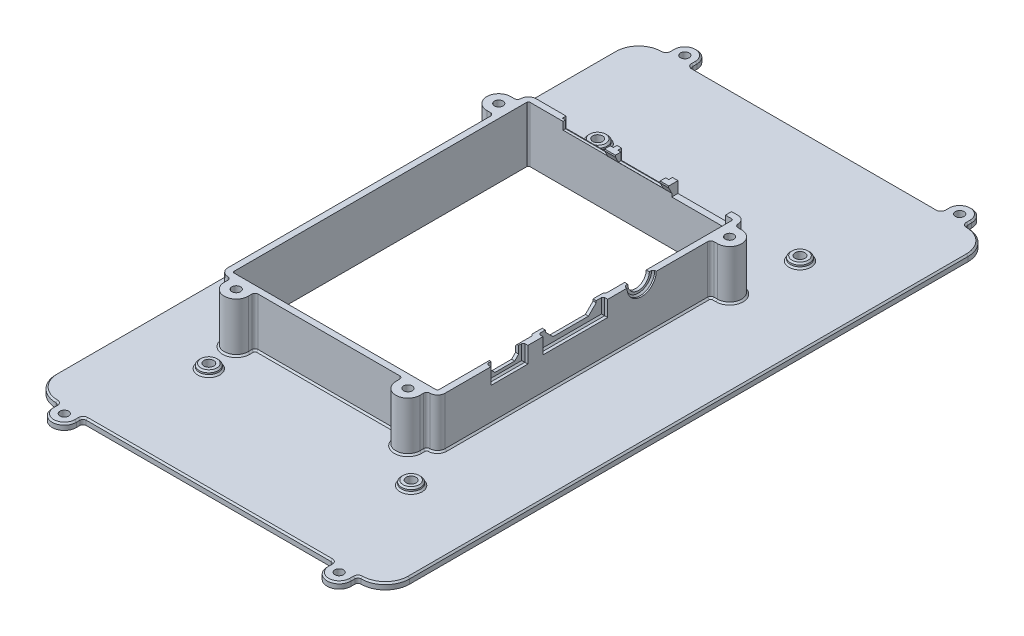
SolidWorks part; units mm, degrees
ref_plane "Front Plane" through (0, 0, 0) normal (0, 0, 1) x (1, 0, 0)
ref_plane "Top Plane" through (0, 0, 0) normal (0, 1, 0) x (1, 0, 0)
ref_plane "Right Plane" through (0, 0, 0) normal (1, 0, 0) x (0, 0, -1)
sketch "Sketch2" plane through (0, 0, 0) normal (0, 1, 0) x (1, 0, 0)
  line L1 (2.5, 0) -> (68, 0)
  line L2 (0, 2.5) -> (0, 97.5)
  line L3 (2.5, 100) -> (68, 100)
  line L4 (70.5, 2.5) -> (70.5, 97.5)
  arc A0 (0, 2.5) -> (2.5, 0) centre (2.5, 2.5) ccw
  arc A1 (68, 0) -> (70.5, 2.5) centre (68, 2.5) ccw
  arc A2 (70.5, 97.5) -> (68, 100) centre (68, 97.5) ccw
  arc A3 (2.5, 100) -> (0, 97.5) centre (2.5, 97.5) ccw
  point P7 (0, 0)
  point P10 (70.5, 0)
  point P13 (70.5, 100)
  point P16 (0, 100)
  dimension "D3" = 2.5
  dimension "D1" = 70.5
  dimension "D2" = 100
extrude "Base" add sketch "Sketch2" along normal blind 16.1
shell "Shell" thickness 2 removed face at (35.25, 16.1, -50) removed face at (35.25, 0, -50)
sketch "Sketch14" plane through (0, 0, 0) normal (0, -1, 0) x (1, 0, 0)
  line L0 (35.25, 0) -> (35.25, -100) construction
  line L2 (68, -100) -> (2.5, -100) construction
  line L3 (-2.2, -88.7) -> (0, -88.7)
  line L4 (0, -97.5) -> (0, -2.5) construction
  line L5 (0, -88.7) -> (0, -96.5)
  line L6 (0, -96.5) -> (-2.2, -96.5)
  line L7 (3.5, 2.2) -> (3.5, 0)
  line L8 (2.5, 0) -> (68, 0) construction
  line L9 (3.5, 0) -> (11.3, 0)
  line L10 (11.3, 0) -> (11.3, 2.2)
  line L11 (72.7, -88.7) -> (70.5, -88.7)
  line L12 (70.5, -96.5) -> (72.7, -96.5)
  line L13 (70.5, -88.7) -> (70.5, -96.5)
  line L14 (59.2, 0) -> (59.2, 2.2)
  line L15 (67, 0) -> (59.2, 0)
  line L16 (67, 2.2) -> (67, 0)
  line L17 (2.5, 0) -> (68, 0) construction
  arc A0 (-2.2, -88.7) -> (-2.2, -96.5) centre (-2.2, -92.6) ccw
  arc A1 (3.5, 2.2) -> (11.3, 2.2) centre (7.4, 2.2) cw
  arc A2 (72.7, -88.7) -> (72.7, -96.5) centre (72.7, -92.6) cw
  arc A3 (67, 2.2) -> (59.2, 2.2) centre (63.1, 2.2) ccw
  dimension "D1" = 2.2
  dimension "D2" = 7.8
  dimension "D3" = 3.5
  dimension "D4" = 3.5
extrude "Board Clamps" add sketch "Sketch14" against normal up to surface (16.1 mm away) up to face at (35.25, 16.1, -50)
fillet "Board Clamp Fillets" radius 1 8 edges at (59.2, 8.05, 0) (67, 8.05, 0) (11.3, 8.05, 0) (3.5, 8.05, 0) (0, 8.05, -96.5) (0, 8.05, -88.7) (70.5, 8.05, -88.7) (70.5, 8.05, -96.5)
sketch "Sketch7" plane through (0, 0, -100) normal (0, 0, -1) x (-1, 0, 0)
  line L0 (-68, 16.1) -> (-2.5, 16.1) construction
  line L1 (-65.95, 16.1) -> (-48.55, 16.1)
  line L2 (-65.95, 16.1) -> (-65.95, 12.5)
  line L3 (-65.95, 12.5) -> (-48.55, 12.5)
  line L4 (-48.55, 16.1) -> (-48.55, 12.5)
  line L5 (-70.5, 16.1) -> (-70.5, 0) construction
  line L6 (-45.75, 16.1) -> (-31.25, 16.1)
  line L7 (-45.75, 16.1) -> (-45.75, 13.63)
  line L8 (-45.75, 13.63) -> (-31.25, 13.63)
  line L9 (-31.25, 16.1) -> (-31.25, 13.63)
  line L10 (-27.75, 16.1) -> (-13.25, 16.1)
  line L11 (-27.75, 16.1) -> (-27.75, 13.63)
  line L12 (-27.75, 13.63) -> (-13.25, 13.63)
  line L13 (-13.25, 16.1) -> (-13.25, 13.63)
  dimension "D1" = 14.5
  dimension "D2" = 2.47
  dimension "D3" = 17.4
  dimension "D4" = 3.6
  dimension "D5" = 4.55
  dimension "D6" = 24.75
  dimension "D7" = 42.75
extrude "IO Cutout" cut sketch "Sketch7" against normal blind 2
sketch "Sketch8" plane through (0, 0, -100) normal (0, 0, -1) x (-1, 0, 0)
  line L6 (-30.25, 12.63) -> (-30.25, 16.1)
  line L7 (-46.75, 12.63) -> (-30.25, 12.63)
  line L8 (-46.75, 16.1) -> (-46.75, 12.63)
  line L9 (-30.25, 12.63) -> (-30.25, 16.1)
  line L10 (-46.75, 12.63) -> (-30.25, 12.63)
  line L11 (-46.75, 16.1) -> (-46.75, 12.63)
  line L12 (-46.75, 16.1) -> (-30.25, 16.1)
  line L13 (-28.75, 16.1) -> (-12.25, 16.1)
  line L15 (-12.25, 12.63) -> (-12.25, 16.1)
  line L16 (-28.75, 12.63) -> (-12.25, 12.63)
  line L17 (-28.75, 16.1) -> (-28.75, 12.63)
  line L18 (-12.25, 12.63) -> (-12.25, 16.1)
  line L19 (-28.75, 12.63) -> (-12.25, 12.63)
  line L20 (-28.75, 16.1) -> (-28.75, 12.63)
  dimension "D1" = 1
  dimension "D2" = 1
extrude "IO Approach" cut sketch "Sketch8" against normal blind 1.2
sketch "Sketch9" plane through (48.55, 0, 0) normal (1, 0, 0) x (0, 0, -1)
  line L0 (98, 16.1) -> (97, 16.1)
  line L1 (97, 16.1) -> (97, 15.55)
  line L2 (97, 15.55) -> (98, 13.55)
  line L3 (98, 13.55) -> (98, 16.1)
  dimension "D1" = 1
  dimension "D2" = 0.55
  dimension "D3" = 2.55
extrude "IO Support" add sketch "Sketch9" against normal up to surface (20.8 mm away) up to face at (27.75, 14.865, -98.4)
sketch "Sketch10" plane through (0, 0, -98) normal (0, 0, -1) x (-1, 0, 0)
  line L1 (-45.75, 16.1) -> (-31.25, 16.1)
  line L2 (-45.75, 16.1) -> (-45.75, 13.63)
  line L3 (-45.75, 13.63) -> (-31.25, 13.63)
  line L4 (-31.25, 16.1) -> (-31.25, 13.63)
extrude "IO Support Cutout" cut sketch "Sketch10" against normal blind 1
sketch "Sketch11" plane through (68.5, 0, 0) normal (-1, 0, 0) x (0, 0, 1)
  line L0 (-2.5, 16.1) -> (-97.5, 16.1) construction
  line L1 (-56.75, 16.1) -> (-32.75, 16.1)
  line L2 (-56.75, 16.1) -> (-56.75, 11.48)
  line L3 (-56.75, 11.48) -> (-32.75, 11.48)
  line L4 (-32.75, 16.1) -> (-32.75, 11.48)
  line L5 (0, 16.1) -> (0, 0) construction
  line L6 (-30.85, 16.1) -> (-15.85, 16.1)
  line L7 (-30.85, 16.1) -> (-30.85, 10.35)
  line L8 (-30.85, 10.35) -> (-15.85, 10.35)
  line L9 (-15.85, 16.1) -> (-15.85, 10.35)
  dimension "D1" = 15.85
  dimension "D2" = 15
  dimension "D3" = 5.75
  dimension "D4" = 4.62
  dimension "D5" = 24
  dimension "D6" = 32.75
extrude "HDMI Support" add sketch "Sketch11" along normal blind 0.5
chamfer "HDMI Support Chamfer" distance 0.5 angle 45 7 edges at (68, 16.1, -23.35) (68, 13.225, -15.85) (68, 10.35, -23.35) (68, 13.225, -30.85) (68, 13.79, -56.75) (68, 11.48, -44.75) (68, 13.79, -32.75)
sketch "Sketch12" plane through (70.5, 0, 0) normal (1, 0, 0) x (0, 0, -1)
  line L0 (2.5, 16.1) -> (87.7, 16.1) construction
  line L1 (17.35, 16.1) -> (29.35, 16.1)
  line L2 (17.35, 16.1) -> (17.35, 10.85)
  line L3 (17.35, 10.85) -> (29.35, 10.85)
  line L4 (29.35, 16.1) -> (29.35, 10.85)
  line L5 (0, 16.1) -> (0, 0) construction
  line L7 (34.25, 16.1) -> (55.25, 16.1)
  line L8 (34.25, 16.1) -> (34.25, 10.98)
  line L9 (34.25, 10.98) -> (55.25, 10.98)
  line L10 (55.25, 16.1) -> (55.25, 10.98)
  dimension "D1" = 17.35
  dimension "D2" = 12
  dimension "D3" = 5.25
  dimension "D4" = 34.25
  dimension "D5" = 21
  dimension "D6" = 5.12
extrude "HDMI Approach" cut sketch "Sketch12" against normal blind 1.5
sketch "Sketch13" plane through (69, 0, 0) normal (1, 0, 0) x (0, 0, -1)
  line L3 (18.85, 16.1) -> (27.85, 16.1)
  line L4 (36.5, 16.1) -> (36.5, 12.98)
  line L5 (55.25, 16.1) -> (34.25, 16.1) construction
  line L6 (27.85, 12.35) -> (27.85, 16.1)
  line L7 (18.85, 12.35) -> (27.85, 12.35)
  line L8 (18.85, 16.1) -> (18.85, 12.35)
  line L9 (27.85, 12.35) -> (27.85, 16.1)
  line L10 (18.85, 12.35) -> (27.85, 12.35)
  line L11 (18.85, 16.1) -> (18.85, 12.35)
  line L12 (36.5, 12.98) -> (53, 12.98)
  line L13 (53, 12.98) -> (53, 16.1)
  line L14 (53, 16.1) -> (36.5, 16.1)
  line L15 (34.25, 16.1) -> (34.25, 10.98) construction
  line L16 (55.25, 10.98) -> (55.25, 16.1) construction
  line L17 (34.25, 10.98) -> (55.25, 10.98) construction
  dimension "D2" = 2.25
  dimension "D3" = 2.25
  dimension "D4" = 2
  dimension "D1" = 1.5
extrude "HDMI Cutout" cut sketch "Sketch13" against normal blind 1
chamfer "HDMI Approach Chamfer" distance 0.5 angle 45 6 edges at (69, 13.475, -17.35) (69, 10.85, -23.35) (69, 13.475, -29.35) (69, 13.54, -34.25) (69, 10.98, -44.75) (69, 13.54, -55.25)
chamfer "USB Chamfer" distance 1.3 angle 45 2 edges at (68.5, 12.35, -18.85) (68.5, 12.35, -27.85)
chamfer "HDMI Chamfer" distance 2.5 angle 45 2 edges at (68.5, 12.98, -36.5) (68.5, 12.98, -53)
sketch "Sketch16" plane through (70.5, 0, 0) normal (1, 0, 0) x (0, 0, -1)
  line L1 (2.5, 16.1) -> (17.35, 16.1) construction
  line L2 (0, 16.1) -> (0, 0) construction
  circle A0 centre (66.25, 16.1) radius 3.5
  dimension "D2" = 7
  dimension "D1" = 66.25
extrude "Audio Cutout" cut sketch "Sketch16" against normal blind 2
sketch "Sketch17" plane through (70.5, 0, 0) normal (1, 0, 0) x (0, 0, -1)
  circle A0 centre (66.25, 16.1) radius 4.75
  dimension "D1" = 9.5
extrude "Audio Approach" cut sketch "Sketch17" against normal blind 1
chamfer "Audio Approach Chamfer" distance 0.5 angle 45 1 edges at (69.5, 11.35, -66.25)
sketch "Board Location" plane through (0, 0, 0) normal (0, 1, 0) x (1, 0, 0)
  line L0 (39.5, 100) -> (39.5, 0) construction
  line L1 (68, 100) -> (65.95, 100) construction
  line L3 (0, 87.7) -> (0, 2.5) construction
  line L4 (12.3, 0) -> (58.2, 0) construction
  line L5 (0, 87.7) -> (0, 2.5) construction
  circle A0 centre (15, 74.25) radius 1.4
  circle A1 centre (15, 16.25) radius 1.4
  circle A2 centre (64, 16.25) radius 1.4
  circle A3 centre (64, 74.25) radius 1.4
  dimension "D1" = 2.8
  dimension "D2" = 25.75
  dimension "D3" = 83.75
  dimension "D4" = 15
  dimension "D5" = 39.5
sketch "Sketch19" plane through (0, 0, 0) normal (0, -1, 0) x (1, 0, 0)
  line L1 (-6.55, 46.74) -> (92.45, 46.74)
  line L2 (-14.43, 38.86) -> (-14.43, -142.34)
  line L3 (-6.55, -150.22) -> (92.45, -150.22)
  line L4 (100.33, 38.86) -> (100.33, -142.34)
  line L12 (2.5, -98) -> (68, -98)
  line L13 (68.5, -97.5) -> (68.5, -2.5)
  line L14 (68, -2) -> (2.5, -2)
  line L15 (2, -2.5) -> (2, -97.5)
  line L16 (2.5, -98) -> (68, -98)
  line L17 (68.5, -97.5) -> (68.5, -2.5)
  line L18 (68, -2) -> (2.5, -2)
  line L19 (2, -2.5) -> (2, -97.5)
  arc A0 (-14.43, -142.34) -> (-6.55, -150.22) centre (-6.55, -142.34) ccw
  arc A1 (92.45, -150.22) -> (100.33, -142.34) centre (92.45, -142.34) ccw
  arc A2 (100.33, 38.86) -> (92.45, 46.74) centre (92.45, 38.86) ccw
  arc A3 (-6.55, 46.74) -> (-14.43, 38.86) centre (-6.55, 38.86) ccw
  arc A12 (2, -97.5) -> (2.5, -98) centre (2.5, -97.5) ccw
  arc A13 (68, -98) -> (68.5, -97.5) centre (68, -97.5) ccw
  arc A14 (68.5, -2.5) -> (68, -2) centre (68, -2.5) ccw
  arc A15 (2.5, -2) -> (2, -2.5) centre (2.5, -2.5) ccw
  arc A16 (2, -97.5) -> (2.5, -98) centre (2.5, -97.5) ccw
  arc A17 (68, -98) -> (68.5, -97.5) centre (68, -97.5) ccw
  arc A18 (68.5, -2.5) -> (68, -2) centre (68, -2.5) ccw
  arc A19 (2.5, -2) -> (2, -2.5) centre (2.5, -2.5) ccw
  point P7 (-14.43, -150.22)
  point P12 (100.33, 46.74)
  point P15 (-14.43, 46.74)
  dimension "D5" = 7.88
  dimension "D1" = 62.99
  dimension "D2" = 29.43
  dimension "D3" = 114.76
  dimension "D4" = 196.96
  dimension "D6" = 0
extrude "Screen Base" add sketch "Sketch19" along normal blind 2
sketch "Sketch15" plane through (0, 16.1, 0) normal (0, 1, 0) x (1, 0, 0)
  circle A0 centre (-2.2, 92.6) radius 1.4
  circle A1 centre (72.7, 92.6) radius 1.4
  circle A2 centre (63.1, -2.2) radius 1.4
  circle A3 centre (7.4, -2.2) radius 1.4
  arc A4 (72.7, 88.7) -> (72.7, 96.5) centre (72.7, 92.6) ccw construction
  dimension "D1" = 2.8
extrude "Board Clamp Taps" cut sketch "Sketch15" against normal through all
sketch "Sketch20" plane through (0, 0, 0) normal (0, 1, 0) x (1, 0, 0)
  circle A0 centre (9.15, 113.35) radius 3.1
  circle A1 centre (74.8, 113.35) radius 3.1
  circle A2 centre (74.8, -12.85) radius 3.1
  circle A3 centre (9.15, -12.85) radius 3.1
  dimension "D5" = 6.2
  dimension "D1" = 29.1
  dimension "D2" = 126.2
  dimension "D3" = 5.85
  dimension "D4" = 65.65
extrude "Leg Supports" add sketch "Sketch20" along normal blind 1.5
sketch "Sketch21" plane through (0, 1.5, 0) normal (0, 1, 0) x (1, 0, 0)
  circle A0 centre (9.15, 113.35) radius 1.6
  circle A1 centre (74.8, 113.35) radius 1.6
  circle A2 centre (74.8, -12.85) radius 1.6
  circle A3 centre (9.15, -12.85) radius 1.6
  circle A4 centre (9.15, 113.35) radius 3.1 construction
  circle A5 centre (74.8, 113.35) radius 3.1 construction
  circle A6 centre (9.15, -12.85) radius 3.1 construction
  circle A7 centre (74.8, -12.85) radius 3.1 construction
  dimension "D1" = 3.2
extrude "Leg Holes" cut sketch "Sketch21" against normal through all
sketch "Sketch22" plane through (0, 0, 0) normal (0, 1, 0) x (1, 0, 0)
  line L0 (-5.55, 152.42) -> (-5.55, 150.22)
  line L1 (-6.55, 150.22) -> (92.45, 150.22) construction
  line L2 (-5.55, 150.22) -> (2.25, 150.22)
  line L3 (2.25, 150.22) -> (2.25, 152.42)
  line L4 (83.65, 152.42) -> (83.65, 150.22)
  line L5 (83.65, 150.22) -> (91.45, 150.22)
  line L6 (91.45, 150.22) -> (91.45, 152.42)
  line L7 (-5.55, -48.94) -> (-5.55, -46.74)
  line L8 (92.45, -46.74) -> (-6.55, -46.74) construction
  line L9 (-5.55, -46.74) -> (2.25, -46.74)
  line L10 (2.25, -46.74) -> (2.25, -48.94)
  line L11 (83.65, -48.94) -> (83.65, -46.74)
  line L12 (83.65, -46.74) -> (91.45, -46.74)
  line L13 (91.45, -46.74) -> (91.45, -48.94)
  line L14 (-14.43, -38.86) -> (-14.43, 142.34) construction
  line L15 (100.33, 142.34) -> (100.33, -38.86) construction
  arc A0 (-5.55, 152.42) -> (2.25, 152.42) centre (-1.65, 152.42) cw
  arc A1 (83.65, 152.42) -> (91.45, 152.42) centre (87.55, 152.42) cw
  arc A2 (-5.55, -48.94) -> (2.25, -48.94) centre (-1.65, -48.94) ccw
  arc A3 (83.65, -48.94) -> (91.45, -48.94) centre (87.55, -48.94) ccw
  dimension "D1" = 8.88
  dimension "D2" = 8.88
  dimension "D3" = 2.2
  dimension "D4" = 7.8
extrude "Screen Clamps" add sketch "Sketch22" against normal up to surface (2 mm away) up to face at (9.15, -2, 14.45)
fillet "Screen Clamp Fillets" radius 1 8 edges at (83.65, -1, 46.74) (-5.55, -1, 46.74) (2.25, -1, 46.74) (91.45, -1, 46.74) (2.25, -1, -150.22) (91.45, -1, -150.22) (83.65, -1, -150.22) (-5.55, -1, -150.22)
sketch "Sketch23" plane through (0, 0, 0) normal (0, 1, 0) x (1, 0, 0)
  circle A0 centre (-1.65, 152.42) radius 1.4
  circle A1 centre (87.55, 152.42) radius 1.4
  circle A2 centre (-1.65, -48.94) radius 1.4
  circle A3 centre (87.55, -48.94) radius 1.4
  arc A4 (2.25, 152.42) -> (-5.55, 152.42) centre (-1.65, 152.42) ccw construction
  arc A5 (91.45, 152.42) -> (83.65, 152.42) centre (87.55, 152.42) ccw construction
  arc A6 (-5.55, -48.94) -> (2.25, -48.94) centre (-1.65, -48.94) ccw construction
  arc A7 (83.65, -48.94) -> (91.45, -48.94) centre (87.55, -48.94) ccw construction
  dimension "D1" = 2.8
extrude "Screen Clamp Taps" cut sketch "Sketch23" against normal through all
chamfer "Shell Chamfer" distance 0.5 angle 45 64 edges at (9.15, 1.5, -110.25) (74.8, 1.5, -110.25) (74.8, 1.5, 15.95) (9.15, 1.5, 15.95) (9.15, 0, 9.75) (74.8, 0, 9.75) (74.8, 0, -116.45) (9.15, 0, -116.45) (-0.2929, 0, -88.4071) (-1.6, 0, -88.7) (-6.1, 0, -92.6) (-1.6, 0, -96.5) (-0.2929, 0, -96.7929) (0.7322, 0, -99.2678) (35.25, 0, -100) (69.7678, 0, -99.2678) (70.7929, 0, -96.7929) (72.1, 0, -96.5) (76.6, 0, -92.6) (72.1, 0, -88.7) (70.7929, 0, -88.4071) (0, 0, -45.1) (0.7322, 0, -0.7322) (3.2071, 0, 0.2929) (3.5, 0, 1.6) (7.4, 0, 6.1) (11.3, 0, 1.6) (11.5929, 0, 0.2929) (35.25, 0, 0) (58.9071, 0, 0.2929) (59.2, 0, 1.6) (70.5, 0, -45.1) (69.7678, 0, -0.7322) (67.2929, 0, 0.2929) (67, 0, 1.6) (63.1, 0, 6.1) (-12.122, 0, -147.912) (-5.8429, 0, -150.5129) (-5.55, 0, -151.82) (-1.65, 0, -156.32) (2.25, 0, -151.82) (2.5429, 0, -150.5129) (42.95, 0, -150.22) (83.3571, 0, -150.5129) (83.65, 0, -151.82) (87.55, 0, -156.32) (91.45, 0, -151.82) (91.7429, 0, -150.5129) (98.022, 0, -147.912) (-14.43, 0, -51.74) (-12.122, 0, 44.432) (-5.8429, 0, 47.0329) (-5.55, 0, 48.34) (-1.65, 0, 52.84) (2.25, 0, 48.34) (2.5429, 0, 47.0329) (100.33, 0, -51.74) (98.022, 0, 44.432) (42.95, 0, 46.74) (83.3571, 0, 47.0329) (83.65, 0, 48.34) (91.7429, 0, 47.0329) (91.45, 0, 48.34) (87.55, 0, 52.84)
